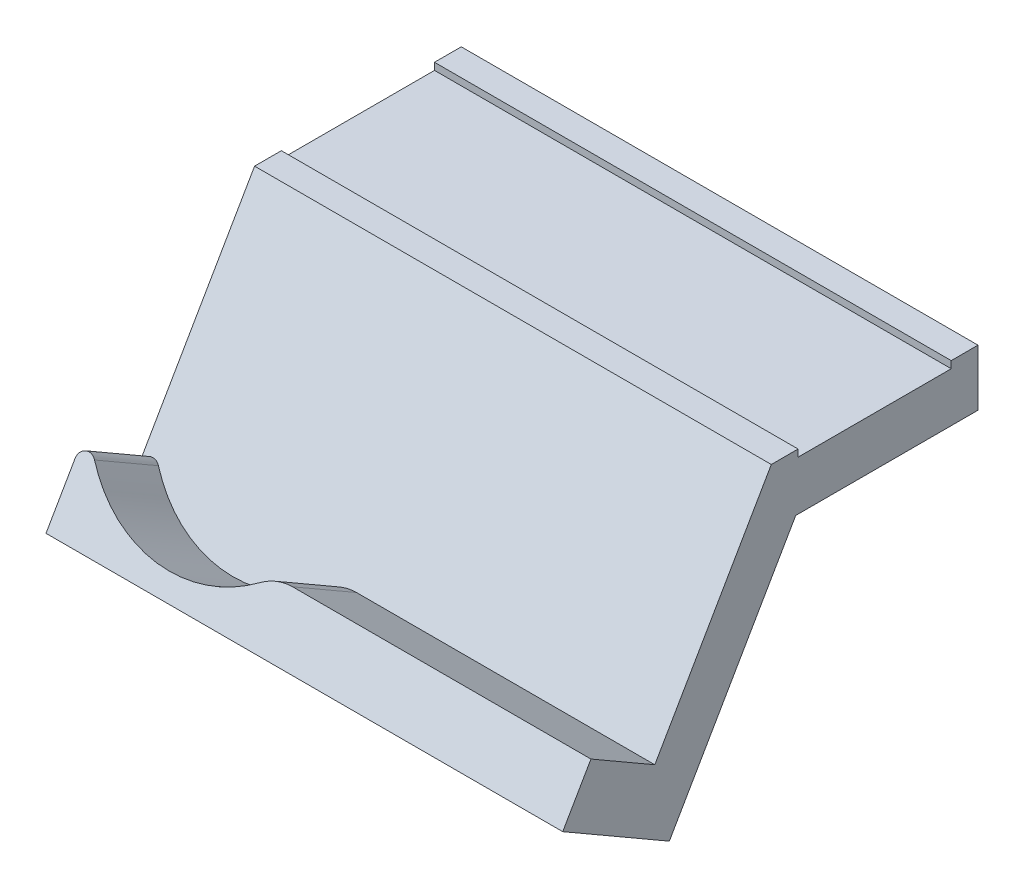
SolidWorks part; units mm, degrees
ref_plane "Front Plane" through (0, 0, 0) normal (0, 0, 1) x (1, 0, 0)
ref_plane "Top Plane" through (0, 0, 0) normal (0, 1, 0) x (1, 0, 0)
ref_plane "Right Plane" through (0, 0, 0) normal (1, 0, 0) x (0, 0, -1)
sketch "Sketch1" plane through (0, 0, 0) normal (0, 1, 0) x (1, 0, 0)
  line L1 (0, 25.95) -> (55, 25.95)
  line L2 (0, 25.95) -> (0, 0)
  line L3 (0, 0) -> (55, 0)
  line L4 (55, 25.95) -> (55, 0)
  dimension "D1" = 55
  dimension "D2" = 25.95
extrude "Boss-Extrude1" add sketch "Sketch1" along normal blind 80 contours L2 L3 L4 L1
sketch "Sketch4" plane through (55, 0, 0) normal (1, 0, 0) x (0, 0, -1)
  line L0 (25.95, 0) -> (0, 0) construction
  line L1 (-77.3025, 60) -> (-27.3025, 146.6025)
  line L2 (-77.3025, 60) -> (9.3, 10)
  line L3 (9.3, 10) -> (59.3, 96.6025)
  line L4 (-27.3025, 146.6025) -> (59.3, 96.6025)
  line L5 (0, 80) -> (0, 0) construction
  dimension "D1" = 100
  dimension "D2" = 100
  dimension "D3" = 10
  dimension "D4" = 9.3
  dimension "D5" = 60
extrude "Cut-Extrude1" cut sketch "Sketch4" against normal blind 50
sketch "Sketch5" plane through (55, 0, 0) normal (1, 0, 0) x (0, 0, -1)
  line L0 (0, 15.3694) -> (0, 0) construction
  line L1 (-11.1603, 10.2657) -> (-6.1603, 18.926)
  line L2 (-11.1603, 10.2657) -> (-2.5, 5.2657)
  line L3 (-2.5, 5.2657) -> (2.5, 13.926)
  line L4 (-6.1603, 18.926) -> (2.5, 13.926)
  line L5 (0, 15.3694) -> (9.3, 10) construction
  dimension "D1" = 10
  dimension "D2" = 10
  dimension "D3" = 2.5
extrude "Cut-Extrude2" cut sketch "Sketch5" against normal through all
sketch "Sketch12" plane through (55, 0, 0) normal (1, 0, 0) x (0, 0, -1)
  line L0 (2.5, 13.926) -> (9.3, 10)
  line L1 (9.3, 10) -> (9.8, 10.866)
  line L2 (9.3, 10) -> (25.95, 38.8386) construction
  line L3 (9.8, 10.866) -> (3, 14.792)
  line L4 (3, 14.792) -> (2.5, 13.926)
  dimension "D1" = 1
extrude "Boss-Extrude2" add sketch "Sketch12" against normal through all contours L3 L4 L0 L1
sketch "Sketch21" plane through (55, 0, 0) normal (1, 0, 0) x (0, 0, -1)
  line L0 (3, 14.792) -> (2.25, 13.493)
  line L1 (0, 9.5959) -> (3, 14.792) construction
  line L2 (2.25, 13.493) -> (9.05, 9.567)
  line L3 (9.05, 9.567) -> (9.8, 10.866)
  line L4 (9.8, 10.866) -> (3, 14.792)
  dimension "D1" = 1.5
extrude "Cut-Extrude10" cut sketch "Sketch21" against normal up to surface (50 mm away) up to face at (5, 36.256, -9.6)
sketch "Sketch6" plane through (0, -1.527, -2.6449) normal (0, 0.5, 0.866) x (1, 0, 0)
  line L0 (55, 8.3103) -> (0, 8.3103) construction
  line L3 (0, 82.257) -> (0, 69.282) construction
  circle A0 centre (12, 22.8103) radius 13.75
  dimension "D1" = 27.5
  dimension "D2" = 14.5
  dimension "D3" = 12
extrude "Cut-Extrude3" cut sketch "Sketch6" along normal through all
ref_axis "Axis2" through (12, 37.0065, 18.4767) along (0, -0.5, -0.866)
sketch "Sketch7" plane through (55, 0, 0) normal (1, 0, 0) x (0, 0, -1)
  line L0 (0, 9.5959) -> (3.8936, 16.3397)
  line L1 (17.4064, 24.0407) -> (10.6936, 12.4137) construction
  line L2 (3.8936, 16.3397) -> (10.6936, 12.4137)
  line L3 (10.6936, 12.4137) -> (66.8017, 109.5959)
  line L4 (66.8017, 109.5959) -> (25.4084, 109.5959)
  line L5 (25.4084, 109.5959) -> (0, 109.5959)
  line L6 (0, 109.5959) -> (0, 9.5959)
  line L7 (10.6936, 12.4137) -> (0, 18.5877) construction
  line L8 (9.05, 9.567) -> (25.95, 38.8386) construction
  dimension "D1" = 100
extrude "Cut-Extrude4" cut sketch "Sketch7" against normal through all contours L5 L6 L0 L2 L3 L4
sketch "Sketch8" plane through (0, 0, 0) normal (0, 1, 0) x (1, 0, 0)
  line L0 (12, -18.4767) -> (12, 1.6454) construction
  line L3 (55, 25.95) -> (0, 25.95) construction
  circle A0 centre (25.75, 27.45) radius 6
  dimension "D1" = 12
  dimension "D3" = 1.5
  dimension "D2" = 13.75
extrude "Cut-Extrude5" cut sketch "Sketch8" along normal through all contours A0
sketch "Sketch9" plane through (55, 0, 0) normal (1, 0, 0) x (0, 0, -1)
  line L0 (21.45, 31.0444) -> (25.95, 31.0444)
  line L1 (25.95, 38.8386) -> (25.95, 0) construction
  line L2 (25.95, 31.0444) -> (25.95, 38.8386)
  line L3 (25.95, 38.8386) -> (21.45, 31.0444)
extrude "Cut-Extrude6" cut sketch "Sketch9" against normal through all
sketch "Sketch10" plane through (0, 0, 0) normal (0, 1, 0) x (1, 0, 0)
  line L0 (0, 21.45) -> (25.75, 21.45) construction
  line L1 (55, 21.45) -> (0, 21.45)
  line L2 (55, 21.45) -> (55, 25.95)
  line L3 (55, 25.95) -> (0, 25.95)
  line L4 (0, 21.45) -> (0, 25.95)
  line L5 (0, 21.45) -> (0, 10.6936) construction
extrude "Cut-Extrude7" cut sketch "Sketch10" along normal through all
fillet "Fillet5" radius 1 1 edges at (0, 14.3767, -7.2936) tangent propagation no
fillet "Fillet6" radius 5 1 edges at (21.4373, 11.53, -5.65)
sketch "Sketch16" plane through (55, 0, 0) normal (1, 0, 0) x (0, 0, -1)
  line L0 (21.45, 20.5444) -> (11.3466, 3.0449)
  line L1 (21.45, 31.0444) -> (21.45, 0) construction
  line L2 (11.3466, 3.0449) -> (0, 9.5959)
  line L3 (0, 9.5959) -> (0, 0)
  line L4 (0, 0) -> (21.45, 0)
  line L5 (21.45, 0) -> (21.45, 20.5444)
  line L6 (9.05, 9.567) -> (21.45, 31.0444) construction
  line L7 (21.45, 0) -> (0, 0) construction
  dimension "D1" = 10.5
extrude "Cut-Extrude8" cut sketch "Sketch16" against normal through all
sketch "Sketch17" plane through (0, 0, -21.45) normal (0, 0, -1) x (-1, 0, 0)
  line L1 (-55, 31.0444) -> (0, 31.0444)
  line L2 (-55, 31.0444) -> (-55, 25.0444)
  line L3 (-55, 25.0444) -> (0, 25.0444)
  line L4 (0, 31.0444) -> (0, 25.0444)
  dimension "D1" = 6
extrude "Boss-Extrude4" add sketch "Sketch17" along normal blind 22
sketch "Sketch18" plane through (55, 0, 0) normal (1, 0, 0) x (0, 0, -1)
  line L0 (16.3983, 11.7946) -> (27.5122, 31.0444)
  line L1 (21.45, 20.5444) -> (11.3466, 3.0449) construction
  line L2 (43.45, 31.0444) -> (21.45, 31.0444) construction
  line L3 (27.5122, 31.0444) -> (21.45, 31.0444)
  line L4 (21.45, 31.0444) -> (11.8517, 14.4196)
  line L5 (9.05, 9.567) -> (21.45, 31.0444) construction
  line L6 (11.8517, 14.4196) -> (16.3983, 11.7946)
extrude "Boss-Extrude5" add sketch "Sketch18" against normal up to surface (55 mm away) contours L0 L3 L4 L6 up to face at (0, 18.997, -20.5633)
sketch "Sketch19" plane through (0, 31.0444, 0) normal (0, 1, 0) x (1, 0, 0)
  line L0 (0, 43.45) -> (0, 21.45) construction
  line L1 (0, 40.6) -> (55, 40.6)
  line L2 (0, 40.6) -> (0, 24.3)
  line L3 (0, 24.3) -> (55, 24.3)
  line L4 (55, 40.6) -> (55, 24.3)
  line L5 (55, 43.45) -> (55, 21.45) construction
  point P8 (0, 32.45)
  dimension "D1" = 16.3
extrude "Cut-Extrude9" cut sketch "Sketch19" against normal blind 0.75
sketch "Sketch20" plane through (55, 0, 0) normal (1, 0, 0) x (0, 0, -1)
  line L0 (0, 9.5959) -> (-0.75, 8.2968)
  line L1 (-0.75, 8.2968) -> (10.5966, 1.7458)
  line L2 (10.5966, 1.7458) -> (11.3466, 3.0449)
  line L3 (11.3466, 3.0449) -> (0, 9.5959)
  line L4 (0, 9.5959) -> (2.25, 13.493) construction
  line L5 (24.0481, 25.0444) -> (11.3466, 3.0449) construction
  dimension "D1" = 1.5
extrude "Boss-Extrude6" add sketch "Sketch20" against normal up to surface (55 mm away) contours L1 L2 L3 L0 up to face at (0, 22.5714, -24.5599)
